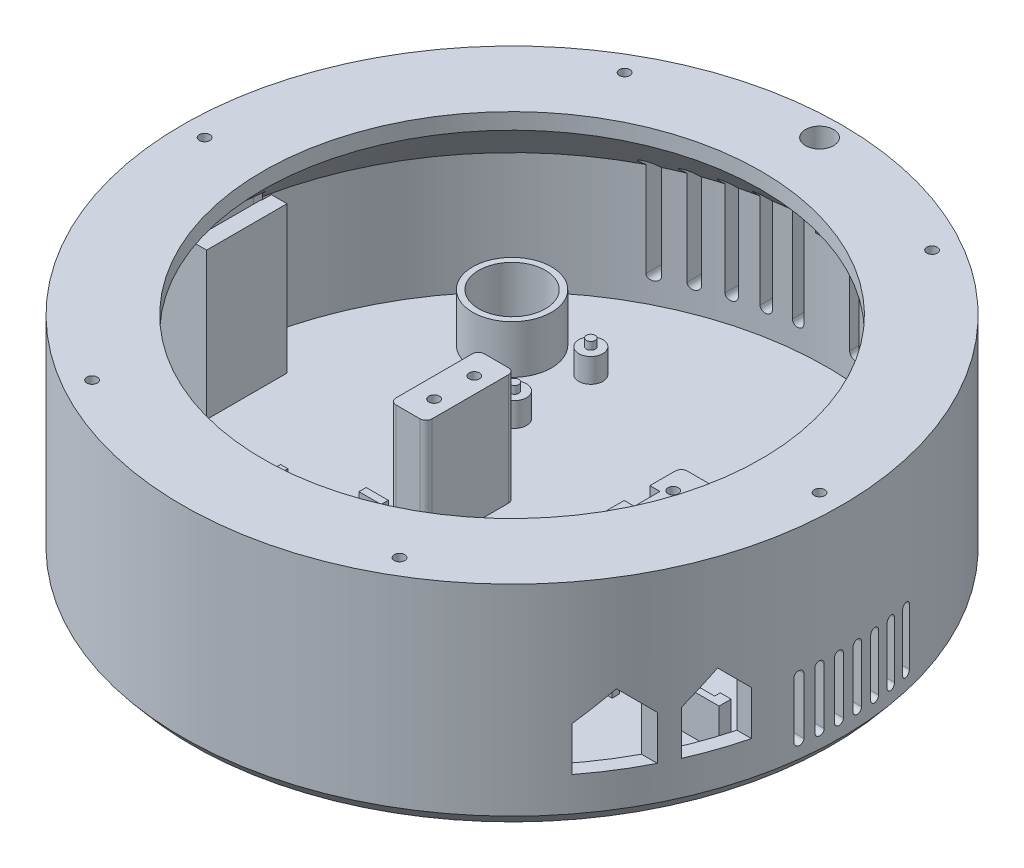
SolidWorks part; units mm, degrees
ref_plane "Front Plane" through (0, 0, 0) normal (0, 0, 1) x (1, 0, 0)
ref_plane "Top Plane" through (0, 0, 0) normal (0, 1, 0) x (1, 0, 0)
ref_plane "Right Plane" through (0, 0, 0) normal (1, 0, 0) x (0, 0, -1)
sketch "Sketch1" plane through (0, 0, 0) normal (0, 0, 1) x (1, 0, 0)
  line L0 (0, -5) -> (0, 80) construction
  line L1 (0, 0) -> (79.5, 0)
  line L2 (79.5, 0) -> (82, 3)
  line L3 (82, 3) -> (82, 53)
  line L4 (82, 53) -> (62, 53)
  line L5 (62, 53) -> (62, 49)
  line L6 (62, 49) -> (78.5, 32.5)
  line L7 (78.5, 32.5) -> (78.5, 2.5)
  line L8 (78.5, 2.5) -> (0, 2.5)
  line L9 (0, 2.5) -> (0, 0)
revolve "Shell + slew ring" add sketch "Sketch1" angle 360 about L0
sketch "Sketch2" plane through (0, 0, 0) normal (0, 1, 0) x (1, 0, 0)
  line L0 (-17.9, 11) -> (-11.9, 11)
  line L1 (-10.4, 9.5) -> (-10.4, -9.5)
  line L2 (-11.9, -11) -> (-17.9, -11)
  line L3 (-19.4, -9.5) -> (-19.4, 9.5)
  line L4 (32.6, 11) -> (38.6, 11)
  line L5 (40.1, 9.5) -> (40.1, -9.5)
  line L6 (38.6, -11) -> (32.6, -11)
  line L7 (31.1, -9.5) -> (31.1, 9.5)
  arc A0 (-19.4, 9.5) -> (-17.9, 11) centre (-17.9, 9.5) cw
  arc A1 (-11.9, 11) -> (-10.4, 9.5) centre (-11.9, 9.5) cw
  arc A2 (-10.4, -9.5) -> (-11.9, -11) centre (-11.9, -9.5) cw
  arc A3 (-17.9, -11) -> (-19.4, -9.5) centre (-17.9, -9.5) cw
  arc A4 (31.1, 9.5) -> (32.6, 11) centre (32.6, 9.5) cw
  arc A5 (38.6, 11) -> (40.1, 9.5) centre (38.6, 9.5) cw
  arc A6 (40.1, -9.5) -> (38.6, -11) centre (38.6, -9.5) cw
  arc A7 (32.6, -11) -> (31.1, -9.5) centre (32.6, -9.5) cw
extrude "Pan servo pillars" add sketch "Sketch2" along normal blind 27.9 from offset 2.3
sketch "Sketch3" plane through (0, 0, 0) normal (0, 1, 0) x (1, 0, 0)
  circle A0 centre (-14.4, 5) radius 1.3
  circle A1 centre (-14.4, -5) radius 1.3
  circle A2 centre (35.1, 5) radius 1.3
  circle A3 centre (35.1, -5) radius 1.3
extrude "Pillar pilot holes" cut sketch "Sketch3" along normal blind 13.2 from offset 17.2
sketch "Sketch4" plane through (0, 0, 0) normal (0, 1, 0) x (1, 0, 0)
  line L0 (30.5, 4.5) -> (40.7, 4.5)
  line L1 (40.7, 4.5) -> (40.7, -4.5)
  line L2 (40.7, -4.5) -> (30.5, -4.5)
  line L3 (30.5, -4.5) -> (30.5, 4.5)
extrude "Servo lead notch" cut sketch "Sketch4" along normal blind 10.7 from offset 2.3
sketch "Sketch5" plane through (0, 0, 0) normal (0, 1, 0) x (1, 0, 0)
  circle A0 centre (-27.9, 47.5) radius 3
  circle A1 centre (-27.9, 28.5) radius 3
  circle A2 centre (27.9, 47.5) radius 3
  circle A3 centre (27.9, 28.5) radius 3
extrude "PCA9685 posts" add sketch "Sketch5" along normal blind 6.2 from offset 2.3
sketch "Sketch6" plane through (0, 0, 0) normal (0, 1, 0) x (1, 0, 0)
  circle A0 centre (-27.9, 47.5) radius 1.1
  circle A1 centre (-27.9, 28.5) radius 1.1
  circle A2 centre (27.9, 47.5) radius 1.1
  circle A3 centre (27.9, 28.5) radius 1.1
extrude "PCA9685 locating pins" add sketch "Sketch6" along normal blind 2.1 from offset 8.3
sketch "Sketch7" plane through (0, 0, 0) normal (0, 1, 0) x (1, 0, 0)
  circle A0 centre (-16.5, -26.5) radius 2.7
  circle A1 centre (-16.5, -43.5) radius 2.7
  circle A2 centre (39.5, -26.5) radius 2.7
  circle A3 centre (39.5, -43.5) radius 2.7
extrude "ESP32 posts" add sketch "Sketch7" along normal blind 10.2 from offset 2.3
sketch "Sketch8" plane through (0, 0, 0) normal (0, 1, 0) x (1, 0, 0)
  line L0 (-13, -19.6) -> (-18.5, -19.6)
  line L1 (-18.5, -19.6) -> (-18.5, -17.8)
  line L2 (-18.5, -17.8) -> (-13, -17.8)
  line L3 (-13, -17.8) -> (-13, -19.6)
  line L4 (-13, -50.4) -> (-18.5, -50.4)
  line L5 (-18.5, -50.4) -> (-18.5, -52.2)
  line L6 (-18.5, -52.2) -> (-13, -52.2)
  line L7 (-13, -52.2) -> (-13, -50.4)
  line L8 (39, -19.6) -> (44.5, -19.6)
  line L9 (44.5, -19.6) -> (44.5, -17.8)
  line L10 (44.5, -17.8) -> (39, -17.8)
  line L11 (39, -17.8) -> (39, -19.6)
  line L12 (39, -50.4) -> (44.5, -50.4)
  line L13 (44.5, -50.4) -> (44.5, -52.2)
  line L14 (44.5, -52.2) -> (39, -52.2)
  line L15 (39, -52.2) -> (39, -50.4)
extrude "ESP32 fences" add sketch "Sketch8" along normal blind 13.2 from offset 2.3
sketch "Sketch9" plane through (0, 0, 0) normal (0, 1, 0) x (1, 0, 0)
  circle A0 centre (-54.5, -27.5) radius 2.7
  circle A1 centre (-54.5, -36) radius 2.7
  circle A2 centre (-39.5, -27.5) radius 2.7
  circle A3 centre (-39.5, -36) radius 2.7
extrude "Amp posts" add sketch "Sketch9" along normal blind 7.7 from offset 2.3
sketch "Sketch10" plane through (0, 0, 0) normal (0, 1, 0) x (1, 0, 0)
  line L0 (-57.4, -26) -> (-59.2, -26)
  line L1 (-59.2, -26) -> (-59.2, -21)
  line L2 (-59.2, -21) -> (-57.4, -21)
  line L3 (-57.4, -21) -> (-57.4, -26)
  line L4 (-57.4, -34) -> (-59.2, -34)
  line L5 (-59.2, -34) -> (-59.2, -39)
  line L6 (-59.2, -39) -> (-57.4, -39)
  line L7 (-57.4, -39) -> (-57.4, -34)
  line L8 (-36.6, -26) -> (-34.8, -26)
  line L9 (-34.8, -26) -> (-34.8, -21)
  line L10 (-34.8, -21) -> (-36.6, -21)
  line L11 (-36.6, -21) -> (-36.6, -26)
  line L12 (-36.6, -34) -> (-34.8, -34)
  line L13 (-34.8, -34) -> (-34.8, -39)
  line L14 (-34.8, -39) -> (-36.6, -39)
  line L15 (-36.6, -39) -> (-36.6, -34)
extrude "Amp fences" add sketch "Sketch10" along normal blind 10.7 from offset 2.3
sketch "Sketch11" plane through (0, 0, 0) normal (0, 1, 0) x (1, 0, 0)
  line L0 (58, -15) -> (69.5, -15)
  line L1 (69.5, -15) -> (69.5, -18)
  line L2 (69.5, -18) -> (58, -18)
  line L3 (58, -18) -> (58, -15)
  line L4 (58, 26) -> (69.5, 26)
  line L5 (69.5, 26) -> (69.5, 23)
  line L6 (69.5, 23) -> (58, 23)
  line L7 (58, 23) -> (58, 26)
extrude "Speaker rails" add sketch "Sketch11" along normal blind 24.2 from offset 2.3
sketch "Sketch12" plane through (0, 0, 0) normal (0, 1, 0) x (1, 0, 0)
  line L0 (60.7, -14.9) -> (66.8, -14.9)
  line L1 (66.8, -14.9) -> (66.8, -16.4)
  line L2 (66.8, -16.4) -> (60.7, -16.4)
  line L3 (60.7, -16.4) -> (60.7, -14.9)
  line L4 (60.7, 24.4) -> (66.8, 24.4)
  line L5 (66.8, 24.4) -> (66.8, 22.9)
  line L6 (66.8, 22.9) -> (60.7, 22.9)
  line L7 (60.7, 22.9) -> (60.7, 24.4)
extrude "Speaker grooves" cut sketch "Sketch12" along normal blind 23.2 from offset 3.5
sketch "Sketch13" plane through (0, 0, 0) normal (0, 1, 0) x (1, 0, 0)
  line L0 (-79.5, 10) -> (-66, 10)
  line L1 (-66, 10) -> (-66, -10)
  line L2 (-66, -10) -> (-79.5, -10)
  line L3 (-79.5, -10) -> (-79.5, 10)
extrude "Mic block" add sketch "Sketch13" along normal blind 36.7 from offset 2.3
sketch "Sketch14" plane through (0, 0, 0) normal (0, 1, 0) x (1, 0, 0)
  line L0 (-71.95, 7.8) -> (-70.05, 7.8)
  line L1 (-70.05, 7.8) -> (-70.05, -7.8)
  line L2 (-70.05, -7.8) -> (-71.95, -7.8)
  line L3 (-71.95, -7.8) -> (-71.95, 7.8)
extrude "Mic slot" cut sketch "Sketch14" along normal blind 17.2 from offset 22
sketch "Sketch15" plane through (0, 0, 0) normal (1, 0, 0) x (0, 0, -1)
  circle A0 centre (0, 30) radius 1.25
extrude "Mic port" cut sketch "Sketch15" along normal blind 19 from offset 90 offset against normal yes
sketch "Sketch16" plane through (0, 0, 0) normal (0, 1, 0) x (1, 0, 0)
  circle A0 centre (-44, 44) radius 9.8
  circle A1 centre (-44, 44) radius 8.3
extrude "Cap clip" add sketch "Sketch16" along normal blind 12.2 from offset 2.3
sketch "Sketch17" plane through (0, 0, 0) normal (1, 0, 0) x (0, 0, -1)
  line L0 (16.9, 7) -> (16.9, 21)
  line L1 (19.1, 21) -> (19.1, 7)
  line L2 (12.2333, 7) -> (12.2333, 21)
  line L3 (14.4333, 21) -> (14.4333, 7)
  line L4 (7.5667, 7) -> (7.5667, 21)
  line L5 (9.7667, 21) -> (9.7667, 7)
  line L6 (2.9, 7) -> (2.9, 21)
  line L7 (5.1, 21) -> (5.1, 7)
  line L8 (-1.7667, 7) -> (-1.7667, 21)
  line L9 (0.4333, 21) -> (0.4333, 7)
  line L10 (-6.4333, 7) -> (-6.4333, 21)
  line L11 (-4.2333, 21) -> (-4.2333, 7)
  line L12 (-11.1, 7) -> (-11.1, 21)
  line L13 (-8.9, 21) -> (-8.9, 7)
  arc A0 (16.9, 21) -> (19.1, 21) centre (18, 21) cw
  arc A1 (19.1, 7) -> (16.9, 7) centre (18, 7) cw
  arc A2 (12.2333, 21) -> (14.4333, 21) centre (13.3333, 21) cw
  arc A3 (14.4333, 7) -> (12.2333, 7) centre (13.3333, 7) cw
  arc A4 (7.5667, 21) -> (9.7667, 21) centre (8.6667, 21) cw
  arc A5 (9.7667, 7) -> (7.5667, 7) centre (8.6667, 7) cw
  arc A6 (2.9, 21) -> (5.1, 21) centre (4, 21) cw
  arc A7 (5.1, 7) -> (2.9, 7) centre (4, 7) cw
  arc A8 (-1.7667, 21) -> (0.4333, 21) centre (-0.6667, 21) cw
  arc A9 (0.4333, 7) -> (-1.7667, 7) centre (-0.6667, 7) cw
  arc A10 (-6.4333, 21) -> (-4.2333, 21) centre (-5.3333, 21) cw
  arc A11 (-4.2333, 7) -> (-6.4333, 7) centre (-5.3333, 7) cw
  arc A12 (-11.1, 21) -> (-8.9, 21) centre (-10, 21) cw
  arc A13 (-8.9, 7) -> (-11.1, 7) centre (-10, 7) cw
extrude "Speaker grille" cut sketch "Sketch17" along normal blind 24 from offset 66
sketch "Sketch18" plane through (0, 0, 0) normal (1, 0, 0) x (0, 0, -1)
  line L0 (-19.97, 11.5) -> (-19.97, 22.5)
  line L1 (-19.97, 22.5) -> (-26.47, 29)
  line L2 (-26.47, 29) -> (-32.97, 22.5)
  line L3 (-32.97, 22.5) -> (-32.97, 11.5)
  line L4 (-32.97, 11.5) -> (-19.97, 11.5)
  line L5 (-37.03, 11.5) -> (-37.03, 22.5)
  line L6 (-37.03, 22.5) -> (-43.53, 29)
  line L7 (-43.53, 29) -> (-50.03, 22.5)
  line L8 (-50.03, 22.5) -> (-50.03, 11.5)
  line L9 (-50.03, 11.5) -> (-37.03, 11.5)
extrude "USB windows" cut sketch "Sketch18" along normal blind 44 from offset 46
sketch "Sketch19" plane through (0, 0, 0) normal (0, 0, 1) x (1, 0, 0)
  line L0 (-36.3, 9) -> (-36.3, 34)
  line L1 (-33.7, 34) -> (-33.7, 9)
  line L2 (-29.3, 9) -> (-29.3, 34)
  line L3 (-26.7, 34) -> (-26.7, 9)
  line L4 (-22.3, 9) -> (-22.3, 34)
  line L5 (-19.7, 34) -> (-19.7, 9)
  line L6 (-15.3, 9) -> (-15.3, 34)
  line L7 (-12.7, 34) -> (-12.7, 9)
  line L8 (-8.3, 9) -> (-8.3, 34)
  line L9 (-5.7, 34) -> (-5.7, 9)
  line L10 (5.7, 9) -> (5.7, 34)
  line L11 (8.3, 34) -> (8.3, 9)
  line L12 (12.7, 9) -> (12.7, 34)
  line L13 (15.3, 34) -> (15.3, 9)
  line L14 (19.7, 9) -> (19.7, 34)
  line L15 (22.3, 34) -> (22.3, 9)
  line L16 (26.7, 9) -> (26.7, 34)
  line L17 (29.3, 34) -> (29.3, 9)
  line L18 (33.7, 9) -> (33.7, 34)
  line L19 (36.3, 34) -> (36.3, 9)
  arc A0 (-36.3, 34) -> (-33.7, 34) centre (-35, 34) cw
  arc A1 (-33.7, 9) -> (-36.3, 9) centre (-35, 9) cw
  arc A2 (-29.3, 34) -> (-26.7, 34) centre (-28, 34) cw
  arc A3 (-26.7, 9) -> (-29.3, 9) centre (-28, 9) cw
  arc A4 (-22.3, 34) -> (-19.7, 34) centre (-21, 34) cw
  arc A5 (-19.7, 9) -> (-22.3, 9) centre (-21, 9) cw
  arc A6 (-15.3, 34) -> (-12.7, 34) centre (-14, 34) cw
  arc A7 (-12.7, 9) -> (-15.3, 9) centre (-14, 9) cw
  arc A8 (-8.3, 34) -> (-5.7, 34) centre (-7, 34) cw
  arc A9 (-5.7, 9) -> (-8.3, 9) centre (-7, 9) cw
  arc A10 (5.7, 34) -> (8.3, 34) centre (7, 34) cw
  arc A11 (8.3, 9) -> (5.7, 9) centre (7, 9) cw
  arc A12 (12.7, 34) -> (15.3, 34) centre (14, 34) cw
  arc A13 (15.3, 9) -> (12.7, 9) centre (14, 9) cw
  arc A14 (19.7, 34) -> (22.3, 34) centre (21, 34) cw
  arc A15 (22.3, 9) -> (19.7, 9) centre (21, 9) cw
  arc A16 (26.7, 34) -> (29.3, 34) centre (28, 34) cw
  arc A17 (29.3, 9) -> (26.7, 9) centre (28, 9) cw
  arc A18 (33.7, 34) -> (36.3, 34) centre (35, 34) cw
  arc A19 (36.3, 9) -> (33.7, 9) centre (35, 9) cw
extrude "Back vents" cut sketch "Sketch19" along normal blind 30 from offset 90 offset against normal yes
sketch "Sketch20" plane through (0, 0, 0) normal (0, 1, 0) x (1, 0, 0)
  circle A0 centre (76.5, 0) radius 1.3
  circle A1 centre (38.25, -66.2509) radius 1.3
  circle A2 centre (-38.25, -66.2509) radius 1.3
  circle A3 centre (-76.5, 0) radius 1.3
  circle A4 centre (-38.25, 66.2509) radius 1.3
  circle A5 centre (38.25, 66.2509) radius 1.3
extrude "Ring pilot holes" cut sketch "Sketch20" along normal blind 12.2 from offset 41
sketch "Sketch21" plane through (0, 0, 0) normal (0, 1, 0) x (1, 0, 0)
  circle A0 centre (0, 76.5) radius 3.5
extrude "MX lead hole" cut sketch "Sketch21" along normal blind 23.2 from offset 30
sketch "Sketch22" plane through (0, 0, 0) normal (0, 1, 0) x (1, 0, 0)
  line L0 (58, -15) -> (69.5, -15)
  line L1 (69.5, -15) -> (69.5, -18)
  line L2 (69.5, -18) -> (58, -18)
  line L3 (58, -18) -> (58, -15)
  line L4 (58, 26) -> (69.5, 26)
  line L5 (69.5, 26) -> (69.5, 23)
  line L6 (69.5, 23) -> (58, 23)
  line L7 (58, 23) -> (58, 26)
extrude "HAND FIX - speaker rails snipped to 10 mm" cut sketch "Sketch22" along normal blind 14.2 from offset 12.5
sketch "Sketch23" plane through (0, 0, 0) normal (0, 1, 0) x (1, 0, 0)
  line L0 (-72.1, 10.2) -> (-69.9, 10.2)
  line L1 (-69.9, 10.2) -> (-69.9, 7.6)
  line L2 (-69.9, 7.6) -> (-72.1, 7.6)
  line L3 (-72.1, 7.6) -> (-72.1, 10.2)
extrude "HAND FIX - mic slot end wall nibbled out" cut sketch "Sketch23" along normal blind 17.2 from offset 22
sketch "Sketch24" plane through (0, 0, 0) normal (0, 1, 0) x (1, 0, 0)
  line L0 (30.6, 3.2) -> (33.6, 3.2)
  line L1 (33.6, 3.2) -> (33.6, -3.2)
  line L2 (33.6, -3.2) -> (30.6, -3.2)
  line L3 (30.6, -3.2) -> (30.6, 3.2)
extrude "HAND FIX - groove for the pan servo's cable boot" cut sketch "Sketch24" along normal blind 17.6 from offset 12.8
